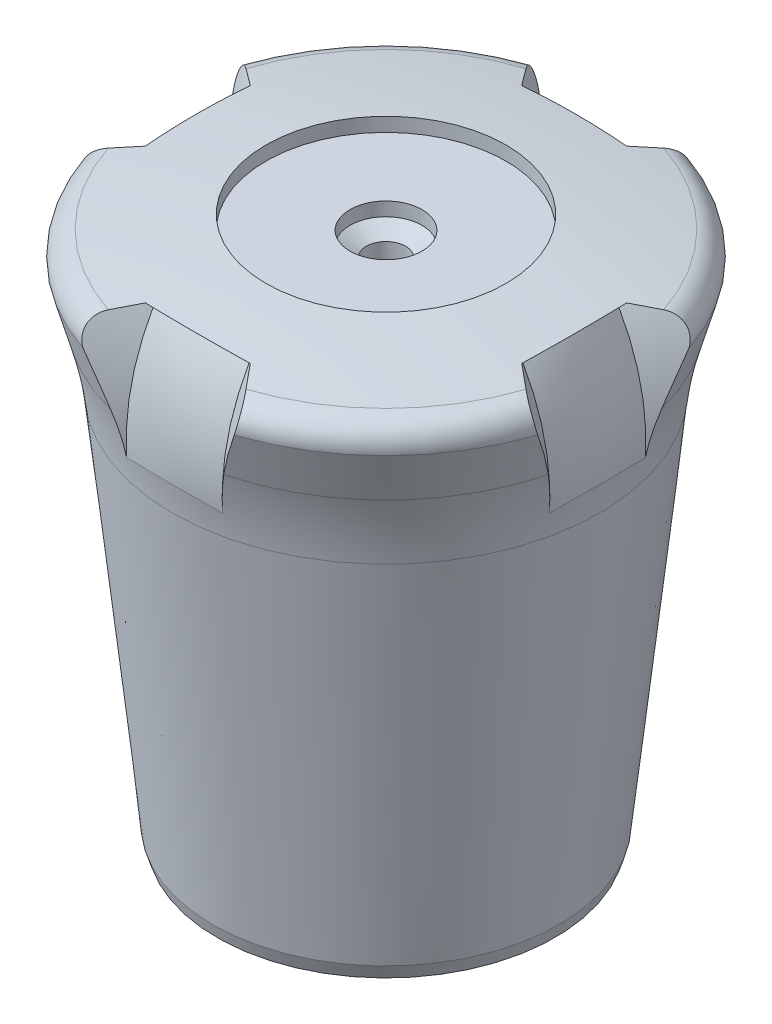
SolidWorks part; units mm, degrees
ref_plane "Front Plane" through (0, 0, 0) normal (0, 0, 1) x (1, 0, 0)
ref_plane "Top Plane" through (0, 0, 0) normal (0, 1, 0) x (1, 0, 0)
ref_plane "Right Plane" through (0, 0, 0) normal (1, 0, 0) x (0, 0, -1)
sketch "Sketch1" plane through (0, 0, 0) normal (0, 0, 1) x (1, 0, 0)
  line L0 (0, 210.9964) -> (0, -210.9964) construction
  line L1 (-190.7083, 0) -> (-22.86, 0) construction
  line L2 (0, 72.39) -> (389.9954, 72.39) construction
  line L3 (32.1183, 169.5772) -> (32.1183, 26.5444) construction
  line L4 (22.86, 0) -> (22.86, -42.5223) construction
  line L5 (-22.86, 0) -> (-22.86, -42.5223) construction
  line L6 (31.7066, 66.436) -> (22.9184, 1.778)
  line L7 (22.352, 0) -> (20.066, 0)
  line L8 (20.066, 0) -> (22.352, 0) construction
  line L9 (20.066, 0) -> (20.066, 47.498)
  line L10 (20.066, 47.498) -> (0, 47.498)
  line L11 (0, 72.39) -> (0, 47.498)
  line L12 (22.9184, 1.778) -> (22.352, 0)
  line L13 (22.86, 0) -> (190.7083, 0) construction
  line L14 (31.7355, 68.2048) -> (31.7355, 76.5845) construction
  arc A0 (29.0798, 69.9958) -> (0, 72.39) centre (0, -105.41) ccw
  arc A2 (29.0798, 69.9958) -> (31.7066, 66.436) centre (28.5605, 66.8636) cw
  point P6 (0, 0)
  point P13 (22.86, 0)
  point P17 (-22.86, 0)
  point P25 (32.1183, 69.465)
  dimension "D1" = 355.6
  dimension "D7" = 3.175
  dimension "D2" = 72.39
  dimension "D3" = 32.1183
  dimension "D4" = 45.72
  dimension "D5" = 40.132
  dimension "D6" = 47.498
  dimension "D8" = 2.286
  dimension "D9" = 1.778
  dimension "D10" = 2.8524
  dimension "D11" = 0.3828
revolve "Revolve1" add sketch "Sketch1" angle 360 about L0
sketch "Sketch2" plane through (0, 0, 0) normal (0, 0, 1) x (1, 0, 0)
  line L0 (0, 96.6315) -> (0, -26.7628) construction
  line L1 (-20.066, 37.1339) -> (-20.066, 65.2994)
  line L2 (-20.066, 65.2994) -> (-9.525, 65.2994)
  line L3 (-9.525, 65.2994) -> (-9.525, 41.0066)
  line L4 (-9.525, 41.0066) -> (-20.066, 37.1339)
  line L5 (-20.066, 47.498) -> (-20.066, 0) construction
  dimension "D1" = 19.05
revolve "Cut-Revolve1" cut sketch "Sketch2" angle 360 about L0
sketch "Sketch3" plane through (0, 47.498, 0) normal (0, -1, 0) x (1, 0, 0)
  circle A0 centre (0, 0) radius 2.6035
  dimension "D1" = 5.207
extrude "Cut-Extrude1" cut sketch "Sketch3" against normal through all
sketch "Sketch4" plane through (0, 0, 0) normal (0, 0, 1) x (1, 0, 0)
  line L0 (31.7066, 66.436) -> (28.702, 55.88)
  line L1 (28.702, 55.88) -> (22.9184, 1.778)
  line L2 (22.9184, 1.778) -> (37.8044, 1.778)
  line L3 (31.7066, 66.436) -> (47.8283, 66.436)
  line L4 (47.8283, 66.436) -> (37.8044, 1.778)
  line L5 (0, 87.3225) -> (0, -15.9061) construction
  line L6 (-22.352, 0) -> (22.352, 0) construction
  dimension "D1" = 55.88
  dimension "D2" = 28.702
revolve "Cut-Revolve2" cut sketch "Sketch4" angle 360 about L5
fillet "Fillet1" radius 50.8 1 edges at (0, 55.88, 28.702)
sketch "Sketch5" plane through (0, 0, 0) normal (0, 0, 1) x (1, 0, 0)
  line L0 (0, 78.8814) -> (0, -5.593) construction
  line L1 (2.6035, 72.3709) -> (-2.6035, 72.3709) construction
  line L2 (0, 75.5962) -> (15.875, 75.5962)
  line L3 (0, 75.5962) -> (0, 66.7124)
  line L4 (4.7625, 69.8309) -> (15.875, 69.8309)
  line L5 (15.875, 75.5962) -> (15.875, 69.8309)
  line L6 (4.7625, 69.8309) -> (4.7625, 68.0268)
  line L7 (4.7625, 68.0268) -> (2.6035, 66.7124)
  line L8 (2.6035, 47.498) -> (2.6035, 72.3709) construction
  line L9 (2.6035, 66.7124) -> (0, 66.7124)
  dimension "D1" = 15.875
  dimension "D2" = 2.54
  dimension "D3" = 4.7625
revolve "Cut-Revolve3" cut sketch "Sketch5" angle 360 about L0
ref_plane "Plane1" through (0, 70.612, 0) normal (0, 1, 0) x (1, 0, 0)
sketch "Sketch6" plane through (0, 0, 0) normal (0, 0, 1) x (1, 0, 0)
  line L0 (-25.0818, 70.612) -> (-30.0082, 73.4563) construction
  line L1 (33.4716, 70.612) -> (-33.4716, 70.612) construction
  arc A0 (-15.875, 71.6799) -> (-29.0798, 69.9958) centre (0, -105.41) ccw construction
  dimension "D1" = 30
ref_plane "Plane2" through (-25.0818, 0, 0) normal (1, 0, 0) x (0, 0, -1)
ref_axis "Axis1" through (-25.0818, 70.612, -33.4716) along (0, 0, 1)
ref_plane "Plane3" through (24.3054, 42.0983, 0) normal (-0.5, -0.866, 0) x (0, 0, 1)
sketch "Sketch8" plane through (0, 47.498, 0) normal (0, -1, 0) x (1, 0, 0)
  line L0 (-3.4544, 3.6148) -> (-3.4544, -3.6148)
  line L1 (0, 6.7131) -> (0, -11.9818) construction
  line L2 (3.4544, 3.6148) -> (3.4544, -3.6148)
  arc A0 (3.4544, 3.6148) -> (-3.4544, 3.6148) centre (0, 0) ccw
  arc A1 (-3.4544, -3.6148) -> (3.4544, -3.6148) centre (0, 0) ccw
  dimension "D1" = 10
  dimension "D2" = 6.9088
extrude "Cut-Extrude2" cut sketch "Sketch8" against normal blind 9.652
sketch "Sketch7" plane through (24.3054, 42.0983, 0) normal (-0.5, -0.866, 0) x (0, 0, 1)
  line L0 (-33.4716, 57.0275) -> (33.4716, 57.0275) construction
  line L1 (0, 33.3562) -> (0, 68.0029) construction
  line L2 (-6.35, 68.8093) -> (-6.35, 51.6273) construction
  line L3 (-6.35, 56.2209) -> (-15.8061, 65.677)
  line L4 (6.35, 56.2209) -> (15.8061, 65.677)
  line L5 (-15.8061, 65.677) -> (15.8061, 65.677)
  line L6 (55.0557, 29.0875) -> (-59.2366, 29.0875) construction
  arc A0 (6.35, 56.2209) -> (-6.35, 56.2209) centre (0, 31.6275) ccw
  dimension "D3" = 45
  dimension "D1" = 25.4
  dimension "D2" = 6.35
  dimension "D4" = 27.94
revolve "Cut-Revolve4" cut sketch "Sketch7" angle 40 about L6 reverse direction yes
ref_axis "Axis2" through (0, 80.3281, 0) along (0, -1, 0)
pattern_circular "CirPattern1" count 4 over 360 about axis through (0, 80.3281, 0) along (0, -1, 0) of "Cut-Revolve4"
